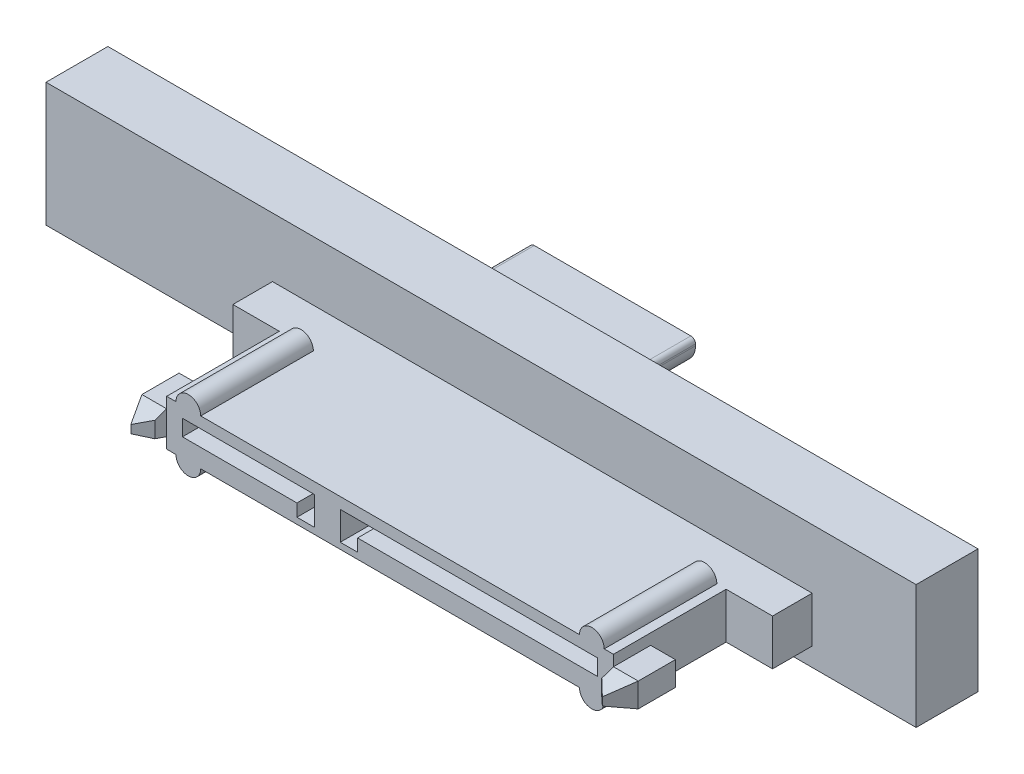
SolidWorks part; units mm, degrees
ref_plane "Front Plane" through (0, 0, 0) normal (0, 0, 1) x (1, 0, 0)
ref_plane "Top Plane" through (0, 0, 0) normal (0, 1, 0) x (1, 0, 0)
ref_plane "Right Plane" through (0, 0, 0) normal (1, 0, 0) x (0, 0, -1)
sketch "Sketch1" plane through (0, 0, 0) normal (0, 0, 1) x (1, 0, 0)
  line L0 (-35.15, 5) -> (35.15, -5) construction
  line L1 (-35.15, 5) -> (35.15, 5)
  line L2 (-35.15, 5) -> (-35.15, -5)
  line L3 (-35.15, -5) -> (35.15, -5)
  line L4 (35.15, 5) -> (35.15, -5)
  dimension "D1" = 10
  dimension "D2" = 70.3
extrude "Boss-Extrude1" add sketch "Sketch1" along normal blind 2.5 and the other way blind 2.5
sketch "Sketch2" plane through (0, 0, 2.5) normal (0, 0, 1) x (1, 0, 0)
  line L0 (35.15, 5) -> (-35.15, 5) construction
  line L1 (-16.85, 0.2) -> (26.75, 0.2)
  line L2 (-16.85, 0.2) -> (-16.85, -3.5)
  line L3 (-16.85, -3.5) -> (26.75, -3.5)
  line L4 (26.75, 0.2) -> (26.75, -3.5)
  line L5 (35.15, -5) -> (35.15, 5) construction
  dimension "D1" = 3.7
  dimension "D2" = 43.6
  dimension "D3" = 4.8
  dimension "D4" = 8.4
extrude "Boss-Extrude2" add sketch "Sketch2" along normal blind 3.2
sketch "Sketch3" plane through (0, 0, 5.7) normal (0, 0, 1) x (1, 0, 0)
  line L0 (-16.85, -1.65) -> (-13.1, -1.65) construction
  line L1 (-13.1, 0.2) -> (-12.35, 0.2)
  line L2 (-13.1, 0.2) -> (-13.1, -3.5)
  line L3 (-13.1, -3.5) -> (-12.35, -3.5)
  line L4 (23, 0.2) -> (23, -3.5)
  line L5 (-16.85, 0.2) -> (-16.85, -3.5) construction
  line L6 (23, -1.65) -> (26.75, -1.65) construction
  line L7 (26.75, -3.5) -> (26.75, 0.2) construction
  line L8 (-11.35, 0.2) -> (-11.35, -3.5) construction
  line L9 (26.75, 0.2) -> (-16.85, 0.2) construction
  line L10 (-10.35, 0.2) -> (20.25, 0.2)
  line L12 (21.25, 0.2) -> (21.25, -3.5) construction
  line L13 (26.75, 0.2) -> (-16.85, 0.2) construction
  line L14 (-16.85, -3.5) -> (26.75, -3.5) construction
  line L15 (-10.35, -3.5) -> (20.25, -3.5)
  line L17 (22.25, 0.2) -> (23, 0.2)
  line L18 (22.25, -3.5) -> (23, -3.5)
  arc A0 (-10.35, 0.2) -> (-12.35, 0.2) centre (-11.35, 0.2) ccw
  arc A1 (-12.35, -3.5) -> (-10.35, -3.5) centre (-11.35, -3.5) ccw
  arc A2 (20.25, 0.2) -> (22.25, 0.2) centre (21.25, 0.2) cw
  arc A3 (22.25, -3.5) -> (20.25, -3.5) centre (21.25, -3.5) cw
  dimension "D3" = 1
  dimension "D1" = 36.1
  dimension "D4" = 0.75
extrude "Boss-Extrude3" add sketch "Sketch3" along normal blind 9.1
sketch "Sketch4" plane through (0, 0, 14.8) normal (0, 0, 1) x (1, 0, 0)
  line L0 (-11.825, -0.7) -> (-1.175, -0.7)
  line L1 (-1.175, -0.7) -> (-1.175, -3)
  line L2 (-1.175, -3) -> (-2.575, -3)
  line L3 (-2.575, -3) -> (-2.575, -2)
  line L4 (-2.575, -2) -> (-11.825, -2)
  line L5 (-11.825, -2) -> (-11.825, -0.7)
  line L6 (0.925, -0.7) -> (21.725, -0.7)
  line L7 (21.725, -0.7) -> (21.725, -2)
  line L8 (21.725, -2) -> (2.325, -2)
  line L9 (2.325, -2) -> (2.325, -3)
  line L10 (2.325, -3) -> (0.925, -3)
  line L11 (0.925, -3) -> (0.925, -0.7)
  line L12 (26.75, 0.2) -> (-16.85, 0.2) construction
  line L13 (-10.35, -3.5) -> (20.25, -3.5) construction
  line L15 (-16.85, -3.5) -> (26.75, -3.5) construction
  line L16 (-13.1, 0.2) -> (-13.1, -3.5) construction
  line L17 (23, -3.5) -> (23, 0.2) construction
  line L18 (23, -3.5) -> (23, 0.2) construction
  line L19 (-13.1, 0.2) -> (-13.1, -3.5) construction
  dimension "D1" = 2.1
  dimension "D2" = 0.9
  dimension "D3" = 1.5
  dimension "D4" = 0.5
  dimension "D5" = 10.65
  dimension "D6" = 1.4
  dimension "D7" = 20.8
  dimension "D8" = 1.275
  dimension "D9" = 1.275
  dimension "D10" = 36.1
extrude "Cut-Extrude1" cut sketch "Sketch4" against normal blind 10
ref_plane "Plane1" through (0, -1.65, 0) normal (0, 1, 0) x (1, 0, 0)
sketch "Sketch5" plane through (0, -1.65, 0) normal (0, 1, 0) x (1, 0, 0)
  line L0 (-13.1, -14.8) -> (-13.1, -5.7) construction
  line L1 (-13.1, -11.8) -> (-15.1, -11.8)
  line L2 (-13.1, -11.8) -> (-13.1, -15.75)
  line L3 (-12.35, -14.8) -> (-10.35, -14.8) construction
  line L4 (-15.1, -11.8) -> (-15.1, -14.8)
  line L5 (4.95, -14.8) -> (4.95, -22.6872) construction
  line L6 (20.25, -14.8) -> (-10.35, -14.8) construction
  line L7 (-13.1, -15.75) -> (-14.1, -16.7)
  line L8 (-14.1, -16.7) -> (-15.1, -14.8)
  line L9 (-13.1, -14.8) -> (-13.1, -16.7) construction
  line L10 (-14.1, -11.8) -> (-14.1, -16.7) construction
  line L11 (-13.1, -16.7) -> (-14.1, -16.7) construction
  line L12 (23, -16.7) -> (24, -16.7) construction
  line L13 (24, -11.8) -> (24, -16.7) construction
  line L14 (23, -14.8) -> (23, -16.7) construction
  line L15 (24, -16.7) -> (25, -14.8)
  line L16 (23, -15.75) -> (24, -16.7)
  line L17 (25, -11.8) -> (25, -14.8)
  line L18 (23, -11.8) -> (23, -15.75)
  line L19 (23, -11.8) -> (25, -11.8)
  dimension "D1" = 2
  dimension "D2" = 3
  dimension "D3" = 1.9
extrude "Boss-Extrude4" add sketch "Sketch5" along normal blind 0.975 and the other way blind 0.975
sketch "Sketch6" plane through (0, 0, 0) normal (1, 0, 0) x (0, 0, -1)
  line L0 (-14.8, -0.675) -> (-16.7, -1.325)
  line L1 (-16.7, -2.625) -> (-16.7, -0.675) construction
  line L2 (-16.7, -1.325) -> (-16.7, -1.975)
  line L3 (-16.7, -1.975) -> (-14.8, -2.625)
  line L4 (-16.7, -0.675) -> (-16.7, -1.325)
  line L5 (-16.7, -1.975) -> (-16.7, -2.625)
  line L6 (-14.8, -0.675) -> (-16.7, -0.675)
  line L7 (-14.8, -2.625) -> (-16.7, -2.625)
extrude "Cut-Extrude2" cut sketch "Sketch6" against normal blind 18.975 and the other way blind 34 contours L0 L6 L4 | L7 L3 L5 region at (0, -2.4083, 16.0667) region at (0, -0.8917, 16.0667)
sketch "Sketch7" plane through (0, 0, -2.5) normal (0, 0, -1) x (-1, 0, 0)
  line L0 (-6.55, 2.9) -> (6.1, 2.9)
  line L1 (6.475, 2.525) -> (6.475, 0.175)
  line L2 (6.1, -0.2) -> (1.75, -0.2)
  line L3 (1.375, 0.175) -> (1.375, 0.7447)
  line L4 (-5.4617, 0.2686) -> (-6.4564, 1.2633)
  line L5 (-1.1377, -0.2) -> (-4.3304, -0.2)
  line L6 (-6.925, 2.3946) -> (-6.925, 2.525)
  line L7 (-0.0064, 0.2686) -> (0.7348, 1.0098)
  line L9 (-35.15, -5) -> (-35.15, 5) construction
  line L10 (-7.35, 3) -> (7.35, 3) construction
  line L11 (-7.35, 3) -> (-7.35, -0.8) construction
  line L12 (-7.35, -0.8) -> (7.35, -0.8) construction
  line L13 (7.35, 3) -> (7.35, -0.8) construction
  line L14 (35.15, 5) -> (35.15, -5) construction
  line L15 (-35.15, 5) -> (35.15, 5) construction
  line L16 (35.15, -5) -> (-35.15, -5) construction
  line L17 (-5.3203, 0.4101) -> (-6.3149, 1.4047)
  line L18 (-1.1377, 0) -> (-4.3304, 0)
  line L19 (-0.1478, 0.4101) -> (0.5934, 1.1513)
  line L20 (1.575, 0.175) -> (1.575, 0.7447)
  line L21 (6.1, 0) -> (1.75, 0)
  line L22 (6.275, 2.525) -> (6.275, 0.175)
  line L23 (-6.55, 2.7) -> (6.1, 2.7)
  line L24 (-6.725, 2.3946) -> (-6.725, 2.525)
  arc A0 (-6.925, 2.3946) -> (-6.4564, 1.2633) centre (-5.325, 2.3946) ccw
  arc A1 (-6.55, 2.9) -> (-6.925, 2.525) centre (-6.55, 2.525) ccw
  arc A2 (-5.4617, 0.2686) -> (-4.3304, -0.2) centre (-4.3304, 1.4) ccw
  arc A3 (-1.1377, -0.2) -> (-0.0064, 0.2686) centre (-1.1377, 1.4) ccw
  arc A4 (1.375, 0.7447) -> (0.7348, 1.0098) centre (1, 0.7447) ccw
  arc A5 (1.375, 0.175) -> (1.75, -0.2) centre (1.75, 0.175) ccw
  arc A6 (6.1, -0.2) -> (6.475, 0.175) centre (6.1, 0.175) ccw
  arc A7 (6.475, 2.525) -> (6.1, 2.9) centre (6.1, 2.525) ccw
  arc A8 (-6.725, 2.3946) -> (-6.3149, 1.4047) centre (-5.325, 2.3946) ccw
  arc A9 (-5.3203, 0.4101) -> (-4.3304, 0) centre (-4.3304, 1.4) ccw
  arc A10 (-1.1377, 0) -> (-0.1478, 0.4101) centre (-1.1377, 1.4) ccw
  arc A11 (1.575, 0.7447) -> (0.5934, 1.1513) centre (1, 0.7447) ccw
  arc A12 (1.575, 0.175) -> (1.75, 0) centre (1.75, 0.175) ccw
  arc A13 (6.1, 0) -> (6.275, 0.175) centre (6.1, 0.175) ccw
  arc A14 (6.275, 2.525) -> (6.1, 2.7) centre (6.1, 2.525) ccw
  arc A15 (-6.55, 2.7) -> (-6.725, 2.525) centre (-6.55, 2.525) ccw
  dimension "D1" = 27.8
  dimension "D2" = 27.8
  dimension "D3" = 2
  dimension "D4" = 4.2
  dimension "D5" = 0.2
extrude "Boss-Extrude5" add sketch "Sketch7" along normal blind 5.4
